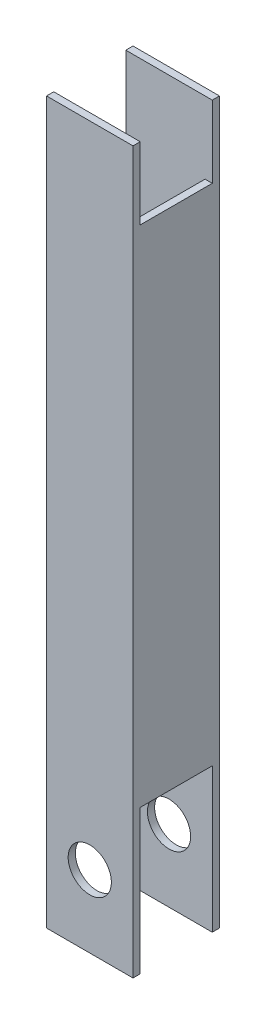
SolidWorks part; units mm, degrees
material "1060 Alloy"
ref_plane "Front Plane" through (0, 0, 0) normal (1, 0, 0) x (0, 1, 0)
ref_plane "Top Plane" through (0, 0, 0) normal (0, 0, 1) x (0, 1, 0)
ref_plane "Right Plane" through (0, 0, 0) normal (0, 1, 0) x (-1, 0, 0)
sketch "Sketch2" plane through (0, 0, 0) normal (0, 1, 0) x (-1, 0, 0)
  line L1 (-30, 30) -> (30, 30)
  line L2 (-30, 30) -> (-30, -30)
  line L3 (-30, -30) -> (30, -30)
  line L4 (30, 30) -> (30, -30)
  line L5 (-30, 30) -> (30, -30) construction
  line L6 (-30, -30) -> (30, 30) construction
  point P0 (0, 0)
  dimension "D1" = 60
  dimension "D2" = 60
extrude "Boss-Extrude1" add sketch "Sketch2" along normal blind 500
shell "Shell1" thickness 5 removed face at (0, 0, 0) removed face at (0, 500, 0)
sketch "Sketch3" plane through (30, 0, 0) normal (1, 0, 0) x (0, 1, 0)
  line L0 (-1000, 0) -> (49000, 0) construction
  line L1 (0, 25) -> (100, 25)
  line L2 (0, 25) -> (0, -25)
  line L3 (0, -25) -> (100, -25)
  line L4 (100, 25) -> (100, -25)
  line L5 (500, 30) -> (0, 30) construction
  line L6 (0, 30) -> (0, -30) construction
  line L7 (500, 30) -> (500, -30) construction
  line L8 (450, 25) -> (500, 25)
  line L9 (450, 25) -> (450, -25)
  line L10 (450, -25) -> (500, -25)
  line L11 (500, 25) -> (500, -25)
  point P7 (0, 0)
  dimension "D1" = 5
  dimension "D2" = 100
  dimension "D3" = 5
  dimension "D4" = 50
extrude "Cut-Extrude1" cut sketch "Sketch3" against normal through all
sketch "Sketch4" plane through (0, 0, 25) normal (0, 0, -1) x (1, 0, 0)
  line L0 (-30, 0) -> (30, -100) construction
  line L1 (30, 0) -> (-30, -100) construction
  line L28 (25, -450) -> (25, -100)
  line L29 (25, -100) -> (30, -100)
  line L38 (30, -100) -> (30, 0)
  line L39 (30, 0) -> (-30, 0)
  line L40 (-30, 0) -> (-30, -100)
  line L41 (-30, -100) -> (-25, -100)
  line L42 (-25, -100) -> (-25, -450)
  line L43 (-25, -450) -> (-30, -450)
  line L44 (-30, -450) -> (-30, -500)
  line L45 (-30, -500) -> (30, -500)
  line L46 (30, -500) -> (30, -450)
  line L47 (30, -450) -> (25, -450)
  line L49 (25, -100) -> (30, -100)
  line L50 (30, -100) -> (30, 0)
  line L51 (30, 0) -> (-30, 0)
  line L52 (-30, 0) -> (-30, -100)
  line L53 (-30, -100) -> (25, -100)
  line L55 (-25, -450) -> (-30, -450)
  circle A0 centre (0, -50) radius 15
  dimension "D2" = 0
  dimension "D1" = 30
extrude "Cut-Extrude3" cut sketch "Sketch4" against normal through all both and the other way through all contours A0 region at (0, 50, 25)
